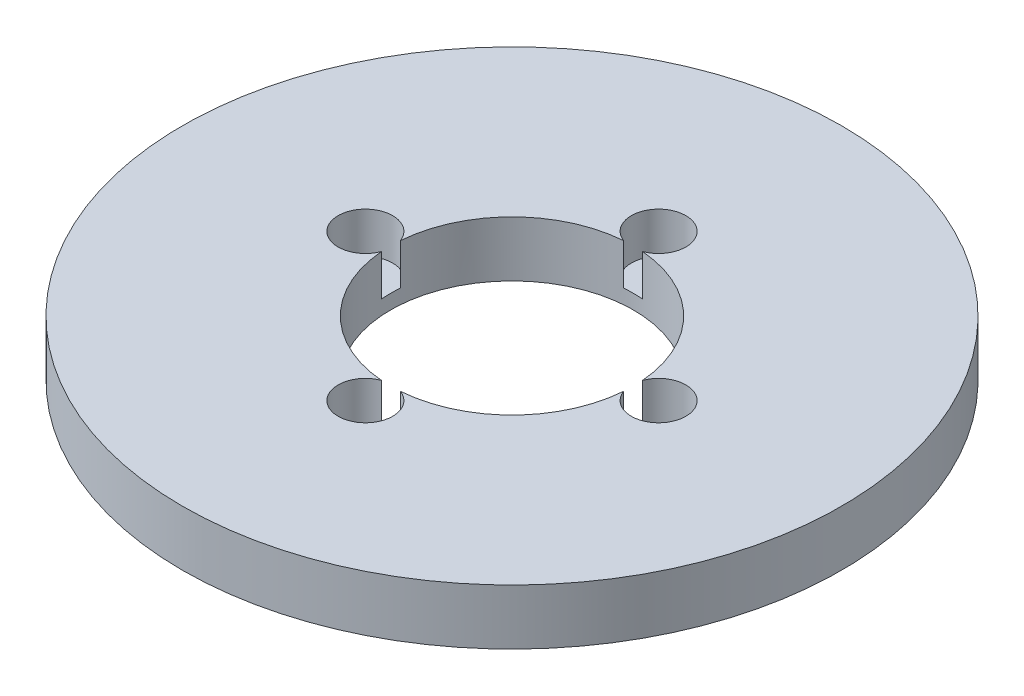
SolidWorks part; units mm, degrees
ref_plane "Front Plane" through (0, 0, 0) normal (0, 0, 1) x (1, 0, 0)
ref_plane "Top Plane" through (0, 0, 0) normal (0, 1, 0) x (1, 0, 0)
ref_plane "Right Plane" through (0, 0, 0) normal (1, 0, 0) x (0, 0, -1)
sketch "Sketch1" plane through (0, 0, 0) normal (0, 1, 0) x (1, 0, 0)
  circle A0 centre (0, 0) radius 95
  dimension "FLANGE_OD" = 190
extrude "Boss-Extrude1" add sketch "Sketch1" along normal blind 16
sketch "Sketch2" plane through (0, 0, 0) normal (0, 1, 0) x (1, 0, 0)
  circle A0 centre (0, 0) radius 35
  dimension "BORE_D" = 70
extrude "Cut-Extrude1" cut sketch "Sketch2" along normal through all
sketch "Sketch3" plane through (0, 16, 0) normal (0, 1, 0) x (1, 0, 0)
  circle A0 centre (0, 0) radius 42.2597 construction
  circle A1 centre (-42.2597, 0) radius 7.8509
  dimension "BOLT_D" = 15.7019
  dimension "BOLT_PCD" = 84.5194
extrude "Cut-Extrude2" cut sketch "Sketch3" against normal blind 11.8459
pattern_circular "CirPattern1" count 4 over 360 about axis through (0, 0, 0) along (0, 1, 0) of "Cut-Extrude2"
